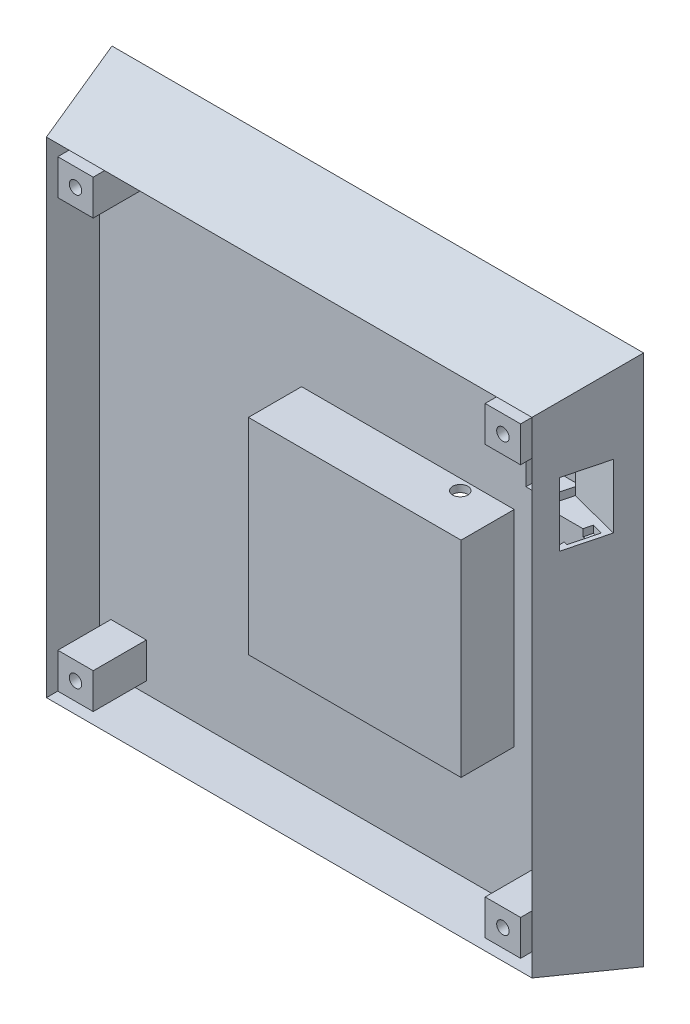
SolidWorks part; units mm, degrees
ref_plane "Plan de face" through (0, 0, 0) normal (0, 0, 1) x (1, 0, 0)
ref_plane "Plan de dessus" through (0, 0, 0) normal (0, 1, 0) x (1, 0, 0)
ref_plane "Plan de droite" through (0, 0, 0) normal (1, 0, 0) x (0, 0, -1)
sketch "Esquisse1" plane through (0, 0, 0) normal (0, 0, 1) x (1, 0, 0)
  line L1 (0, 0) -> (150, 0)
  line L2 (0, 0) -> (0, 150)
  line L3 (0, 150) -> (150, 150)
  line L4 (150, 0) -> (150, 150)
  dimension "D1" = 150
  dimension "D2" = 150
extrude "Boss.-Extru.1" add sketch "Esquisse1" along normal blind 25
chamfer "Chanfrein1" distance 25 distance2 6.5 4 edges at (75, 150, 25) (0, 75, 25) (75, 0, 25) (150, 75, 25) first distance on face at (75, 150, 12.5) first distance on face at (0, 75, 12.5) first distance on face at (75, 0, 12.5) first distance on face at (150, 75, 12.5)
sketch "Esquisse2" plane through (0, 0, 25) normal (0, 0, 1) x (1, 0, 0)
  line L1 (6.5, 143.5) -> (143.5, 143.5)
  line L2 (6.5, 143.5) -> (6.5, 6.5)
  line L3 (6.5, 6.5) -> (143.5, 6.5)
  line L4 (143.5, 143.5) -> (143.5, 6.5)
  line L5 (9.7, 140.3) -> (19.7, 140.3)
  line L6 (9.7, 140.3) -> (9.7, 130.3)
  line L7 (9.7, 130.3) -> (19.7, 130.3)
  line L8 (19.7, 140.3) -> (19.7, 130.3)
  line L9 (140.3, 140.3) -> (130.3, 140.3)
  line L10 (140.3, 140.3) -> (140.3, 130.3)
  line L11 (140.3, 130.3) -> (130.3, 130.3)
  line L12 (130.3, 140.3) -> (130.3, 130.3)
  line L13 (140.3, 9.7) -> (130.3, 9.7)
  line L14 (140.3, 9.7) -> (140.3, 19.7)
  line L15 (140.3, 19.7) -> (130.3, 19.7)
  line L16 (130.3, 9.7) -> (130.3, 19.7)
  line L17 (9.7, 9.7) -> (19.7, 9.7)
  line L18 (9.7, 9.7) -> (9.7, 19.7)
  line L19 (9.7, 19.7) -> (19.7, 19.7)
  line L20 (19.7, 9.7) -> (19.7, 19.7)
  line L21 (123.5, 103.5) -> (63.5, 103.5)
  line L22 (123.5, 103.5) -> (123.5, 45.5)
  line L23 (123.5, 45.5) -> (63.5, 45.5)
  line L24 (63.5, 103.5) -> (63.5, 45.5)
  circle A0 centre (14.7, 135.3) radius 1.75
  circle A1 centre (135.3, 135.3) radius 1.75
  circle A2 centre (135.3, 14.7) radius 1.75
  circle A3 centre (14.7, 14.7) radius 1.75
  line M1 (143.5, 6.5) -> (143.5, 143.5)
  line M2 (143.5, 143.5) -> (6.5, 143.5)
  line M3 (6.5, 143.5) -> (6.5, 6.5)
  line M4 (6.5, 6.5) -> (143.5, 6.5)
  dimension "D9" = 3.5
  dimension "D1" = 3.2
  dimension "D2" = 3.2
  dimension "D3" = 3.2
  dimension "D4" = 3.2
  dimension "D5" = 3.2
  dimension "D6" = 3.2
  dimension "D7" = 3.2
  dimension "D8" = 3.2
  dimension "D10" = 10
  dimension "D11" = 60
  dimension "D12" = 58
  dimension "D13" = 40
  dimension "D14" = 20
extrude "Enlèv. mat.-Extru.2" cut sketch "Esquisse2" against normal blind 15 contours L20 L17 L18 L19 L5 L8 L7 L6 L12 L9 L10 L11 L13 L16 L15 L14 M4 M1 M2 M3 | A0 | A1 | A2 | A3 region at (75, 141.5625, 25) region at (14.7, 135.3, 25) region at (135.3, 135.3, 25) region at (135.3, 14.7, 25) region at (14.7, 14.7, 25)
sketch "Esquisse3" plane through (140.5021, 0, 36.5305) normal (0.9678, 0, 0.2516) x (0.2516, 0, -0.9678)
  line L0 (37.7451, 0) -> (37.7451, 150) construction
  line L1 (18.2451, 126.5) -> (30.7451, 126.5)
  line L2 (18.2451, 126.5) -> (18.2451, 108.5)
  line L3 (18.2451, 108.5) -> (30.7451, 108.5)
  line L4 (30.7451, 126.5) -> (30.7451, 108.5)
  dimension "D1" = 12.5
  dimension "D2" = 18
  dimension "D3" = 7
  dimension "D4" = 17
extrude "Enlèv. mat.-Extru.3" cut sketch "Esquisse3" against normal blind 15
sketch "Esquisse4" plane through (0, 108.5, 0) normal (0, 1, 0) x (1, 0, 0)
  line L0 (146.5417, -8.4676) -> (144.5474, -16.1381)
  line L1 (144.5474, -16.1381) -> (141.512, -15.3489)
  line L2 (141.512, -15.3489) -> (143.5064, -7.6784)
  line L3 (143.5064, -7.6784) -> (146.5417, -8.4676)
  line L4 (143.5, -25) -> (150, 0) construction
extrude "Enlèv. mat.-Extru.4" cut sketch "Esquisse4" against normal blind 2 and the other way blind 20
sketch "Esquisse5" plane through (0, 0, 0) normal (0, 0, -1) x (-1, 0, 0)
  line L0 (-123.5, 103.5) -> (-63.5, 103.5) construction
  line L1 (-121.5, 101.5) -> (-65.5, 101.5)
  line L2 (-121.5, 101.5) -> (-121.5, 47.5)
  line L3 (-121.5, 47.5) -> (-65.5, 47.5)
  line L4 (-65.5, 101.5) -> (-65.5, 47.5)
  line L5 (-123.5, 103.5) -> (-123.5, 45.5) construction
  line L6 (-63.5, 103.5) -> (-63.5, 45.5) construction
  line L7 (-123.5, 45.5) -> (-63.5, 45.5) construction
  line L8 (-125.9123, 143.5) -> (-25.602, 143.5)
  line L9 (-143.5, 143.5) -> (-6.5, 143.5) construction
  line L10 (-25.602, 143.5) -> (-25.602, 125.0727)
  line L11 (-25.602, 125.0727) -> (-6.5, 125.0727)
  line L12 (-6.5, 143.5) -> (-6.5, 6.5) construction
  line L13 (-6.5, 125.0727) -> (-6.5, 27.1738)
  line L14 (-6.5, 27.1738) -> (-25.602, 27.1738)
  line L15 (-25.602, 27.1738) -> (-25.602, 6.5)
  line L16 (-6.5, 6.5) -> (-143.5, 6.5) construction
  line L17 (-25.602, 6.5) -> (-125.9123, 6.5)
  line L18 (-125.9123, 6.5) -> (-125.9123, 27.1738)
  line L19 (-125.9123, 27.1738) -> (-143.5, 27.1738)
  line L20 (-143.5, 6.5) -> (-143.5, 106.5) construction
  line L21 (-143.5, 27.1738) -> (-143.5, 103.3987)
  line L22 (-143.5, 103.3987) -> (-125.9123, 103.3987)
  line L23 (-125.9123, 103.3987) -> (-125.9123, 143.5)
  line L25 (-123.5, 103.5) -> (-63.5, 103.5)
  line L26 (-123.5, 103.5) -> (-123.5, 45.5)
  line L27 (-123.5, 45.5) -> (-63.5, 45.5)
  line L28 (-63.5, 103.5) -> (-63.5, 45.5)
  dimension "D1" = 2
  dimension "D2" = 2
  dimension "D3" = 2
  dimension "D4" = 2
sketch "Esquisse6" plane through (0, 0, 0) normal (0, 0, -1) x (-1, 0, 0)
  line L1 (-123.5, 45.5) -> (-63.5, 45.5) construction
  line L2 (-65.5, 47.5) -> (-121.5, 47.5)
  line L3 (-65.5, 47.5) -> (-65.5, 101.5)
  line L4 (-65.5, 101.5) -> (-121.5, 101.5)
  line L5 (-121.5, 47.5) -> (-121.5, 101.5)
  line L6 (-63.5, 103.5) -> (-63.5, 45.5) construction
  line L7 (-123.5, 103.5) -> (-123.5, 45.5) construction
  line L8 (-123.5, 103.5) -> (-63.5, 103.5) construction
  dimension "D1" = 2
  dimension "D2" = 2
  dimension "D3" = 2
  dimension "D4" = 2
extrude "Enlèv. mat.-Extru.7" cut sketch "Esquisse5" against normal blind 8 contours L4 L1 L2 L3 | L23 L22 L21 L19 L18 L17 L15 L14 L13 L11 L10 L8 L25 L28 L27 L26 region at (93.5, 74.5, 0) region at (75.7571, 141.5625, 0)
extrude "Enlèv. mat.-Extru.6" cut sketch "Esquisse6" against normal blind 22
sketch "Esquisse7" plane through (0, 101.6404, 0) normal (0, -1, 0) x (1, 0, 0)
  line L0 (65.5, 22) -> (65.5, 0) construction
  line L1 (70.5, 6) -> (78.5, 6)
  line L2 (70.5, 6) -> (70.5, 2)
  line L3 (70.5, 2) -> (78.5, 2)
  line L4 (78.5, 6) -> (78.5, 2)
  line L5 (108.5, 6) -> (116.5, 6)
  line L6 (108.5, 6) -> (108.5, 2)
  line L7 (108.5, 2) -> (116.5, 2)
  line L8 (116.5, 6) -> (116.5, 2)
  line L9 (121.5, 22) -> (121.5, 0) construction
  line L10 (150, 0) -> (0, 0) construction
  dimension "D1" = 8
  dimension "D2" = 8
  dimension "D3" = 4
  dimension "D4" = 4
  dimension "D5" = 5
  dimension "D6" = 5
  dimension "D7" = 2
  dimension "D8" = 2
extrude "Enlèv. mat.-Extru.13" cut sketch "Esquisse7" against normal blind 8
sketch "Esquisse8" plane through (0, 103.5, 0) normal (0, 1, 0) x (1, 0, 0)
  circle A0 centre (111.298, -13.0171) radius 2.1448
extrude "Enlèv. mat.-Extru.9" cut sketch "Esquisse8" against normal blind 8
sketch "Esquisse9" plane through (0, 0, 0) normal (0, 0, -1) x (-1, 0, 0)
  circle A0 centre (-135.3, 135.3) radius 4.4852
  circle A1 centre (-14.7, 135.3) radius 4.6901
  circle A2 centre (-14.7, 14.7) radius 4.771
  circle A3 centre (-135.3, 14.7) radius 4.4984
extrude "Enlèv. mat.-Extru.10" cut sketch "Esquisse9" against normal blind 22
sketch "Esquisse10" plane through (0, 0, 10) normal (0, 0, 1) x (1, 0, 0)
  line L0 (133.7212, 108.5) -> (133.7212, 126.5) construction
  line L1 (133.7212, 118.8027) -> (126.8075, 118.8027)
  line L2 (133.7212, 118.8027) -> (133.7212, 110.6918)
  line L3 (133.7212, 110.6918) -> (126.8075, 110.6918)
  line L4 (126.8075, 118.8027) -> (126.8075, 110.6918)
extrude "Enlèv. mat.-Extru.11" cut sketch "Esquisse10" against normal blind 8
sketch "Esquisse11" plane through (0, 47.3596, 0) normal (0, 1, 0) x (1, 0, 0)
  line L1 (89.5, -2) -> (99.5, -2)
  line L2 (89.5, -2) -> (89.5, -6)
  line L3 (89.5, -6) -> (99.5, -6)
  line L4 (99.5, -2) -> (99.5, -6)
  line L7 (0, 0) -> (150, 0) construction
  line L8 (65.5, -22) -> (65.5, 0) construction
  dimension "D1" = 2
  dimension "D2" = 24
extrude "Enlèv. mat.-Extru.12" cut sketch "Esquisse11" against normal blind 8
